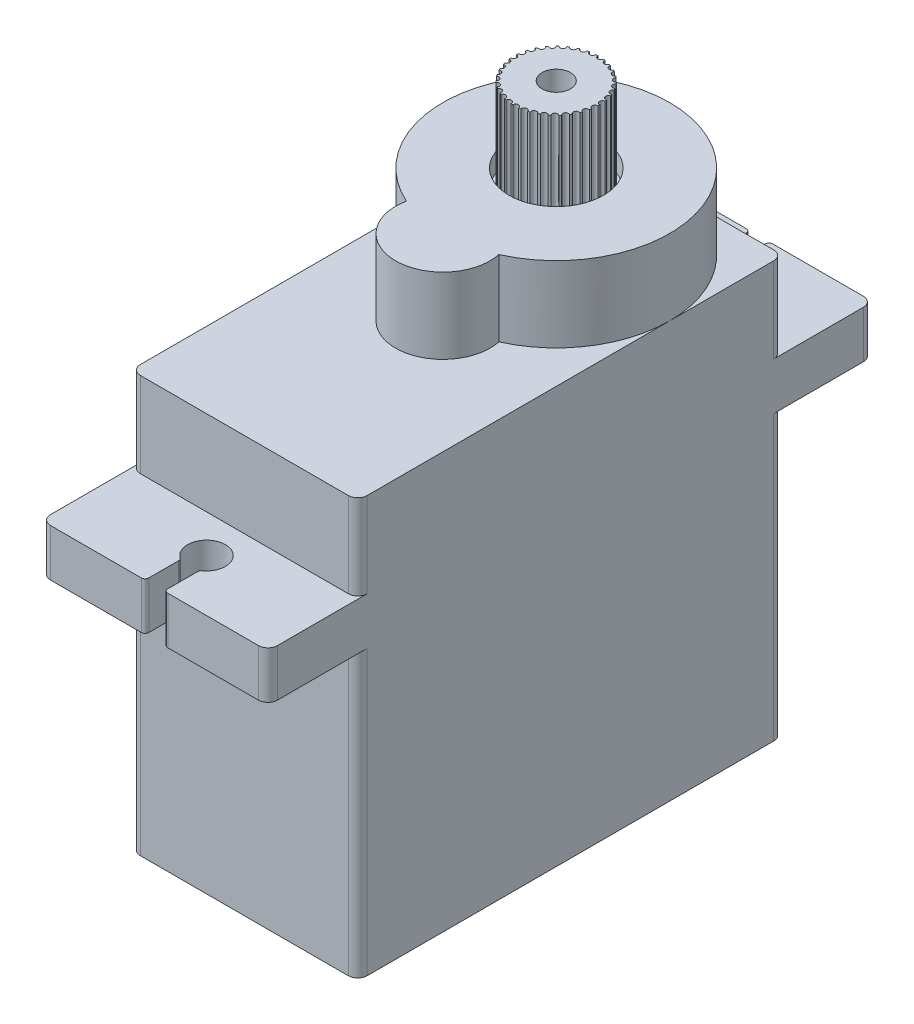
SolidWorks part; units mm, degrees
ref_plane "Ön Düzlem" through (0, 0, 0) normal (0, 0, 1) x (1, 0, 0)
ref_plane "Üst Düzlem" through (0, 0, 0) normal (0, 1, 0) x (1, 0, 0)
ref_plane "Sağ Düzlem" through (0, 0, 0) normal (1, 0, 0) x (0, 0, -1)
sketch "Çizim1" plane through (0, 0, 0) normal (0, 1, 0) x (1, 0, 0)
  line L1 (-5.5, 11.25) -> (5.5, 11.25)
  line L2 (-6, 10.75) -> (-6, -10.75)
  line L3 (-5.5, -11.25) -> (5.5, -11.25)
  line L4 (6, 10.75) -> (6, -10.75)
  line L5 (-6, 11.25) -> (6, -11.25) construction
  line L6 (-6, -11.25) -> (6, 11.25) construction
  arc A0 (5.5, -11.25) -> (6, -10.75) centre (5.5, -10.75) ccw
  arc A1 (-6, -10.75) -> (-5.5, -11.25) centre (-5.5, -10.75) ccw
  arc A2 (5.5, 11.25) -> (6, 10.75) centre (5.5, 10.75) cw
  arc A3 (-5.5, 11.25) -> (-6, 10.75) centre (-5.5, 10.75) ccw
  point P0 (0, 0)
  dimension "D3" = 0.5
  dimension "D1" = 12
  dimension "D2" = 22.5
extrude "Yükseklik-Ekstrüzyon1" add sketch "Çizim1" along normal blind 1
sketch "Çizim2" plane through (0, 1, 0) normal (0, 1, 0) x (1, 0, 0)
  line L0 (-5, 9.25) -> (-5, -9.25)
  line L1 (-5.5, 11.25) -> (5.5, 11.25)
  line L2 (-6, 10.75) -> (-6, -10.75)
  line L3 (-5.5, -11.25) -> (5.5, -11.25)
  line L4 (6, 10.75) -> (6, -10.75)
  line L5 (-6, 11.25) -> (-5.8961, 11.0552) construction
  line L6 (-6, -11.25) -> (-5.8961, -11.0552) construction
  line L7 (-4, -10.25) -> (4, -10.25)
  line L8 (5, 9.25) -> (5, -9.25)
  line L9 (-4, 10.25) -> (4, 10.25)
  line L10 (-6, -11.25) -> (6, -11.25) construction
  line L11 (6, 11.25) -> (6, -11.25) construction
  line L12 (-6, 11.25) -> (-6, -11.25) construction
  line L13 (-6, 11.25) -> (6, 11.25) construction
  line L14 (-5, 10.25) -> (5, 10.25) construction
  line L15 (-5, 10.25) -> (-5, -10.25) construction
  line L16 (-4.9345, 9.2521) -> (4.9345, -9.2521) construction
  line L17 (5, 10.25) -> (5, -10.25) construction
  line L18 (5.8961, 11.0552) -> (6, 11.25) construction
  line L19 (-5, -10.25) -> (5, -10.25) construction
  line L20 (5.8961, -11.0552) -> (6, -11.25) construction
  line L21 (-4.9345, -9.2521) -> (4.9345, 9.2521) construction
  arc A0 (5.5, -11.25) -> (6, -10.75) centre (5.5, -10.75) ccw
  arc A1 (-6, -10.75) -> (-5.5, -11.25) centre (-5.5, -10.75) ccw
  arc A2 (5.5, 11.25) -> (6, 10.75) centre (5.5, 10.75) cw
  arc A3 (-5.5, 11.25) -> (-6, 10.75) centre (-5.5, 10.75) ccw
  arc A5 (4, 10.25) -> (5, 9.25) centre (5, 10.25) ccw
  arc A7 (-4, -10.25) -> (-5, -9.25) centre (-5, -10.25) ccw
  arc A8 (-5, 9.25) -> (-4, 10.25) centre (-5, 10.25) ccw
  arc A9 (5, -9.25) -> (4, -10.25) centre (5, -10.25) ccw
  point P0 (0, 0)
  dimension "D2" = 0.5
  dimension "D1" = 1
extrude "Yükseklik-Ekstrüzyon2" add sketch "Çizim2" along normal blind 5
sketch "Çizim3" plane through (0, 6, 0) normal (0, 1, 0) x (1, 0, 0)
  line L0 (0, -10.25) -> (0, -11.25) construction
  line L1 (-4, -10.25) -> (4, -10.25) construction
  line L2 (-5.5, -11.25) -> (5.5, -11.25) construction
  line L3 (0, -11.25) -> (0, -10.75) construction
  line L4 (0, -10.75) -> (2.4368, -10.75) construction
  line L6 (-2, -10.25) -> (2, -10.25)
  line L7 (-2, -10.25) -> (-2, -11.25)
  line L8 (-2, -11.25) -> (2, -11.25)
  line L9 (2, -10.25) -> (2, -11.25)
  line L10 (-2, -10.25) -> (2, -11.25) construction
  line L11 (-2, -11.25) -> (2, -10.25) construction
  dimension "D1" = 4
extrude "Kes-Ekstrüzyon1" cut sketch "Çizim3" against normal blind 1
fillet "Radyus1" radius 0.1 2 edges at (2, 5, 10.75) (-2, 5, 10.75)
sketch "Çizim4" plane through (0, 6, 0) normal (0, 1, 0) x (1, 0, 0)
  line L0 (-4, 10.25) -> (4, 10.25)
  line L1 (-5.5, 11.25) -> (5.5, 11.25)
  line L2 (-6, 10.75) -> (-6, -10.75)
  line L3 (-5.5, -11.25) -> (5.5, -11.25)
  line L4 (6, 10.75) -> (6, -10.75)
  line L5 (-6, 11.25) -> (-5.8961, 11.0552) construction
  line L6 (-6, -11.25) -> (-5.8961, -11.0552) construction
  line L7 (-4, 10.25) -> (4, 10.25)
  line L8 (5, 9.25) -> (5, -9.25)
  line L9 (5, -9.25) -> (5, 9.25)
  line L10 (-4, 10.25) -> (4, 10.25)
  line L11 (5, 9.25) -> (5, -9.25)
  line L12 (-4, -10.25) -> (4, -10.25)
  line L13 (-5, 9.25) -> (-5, -9.25)
  line L14 (-4.9345, 9.2521) -> (4.9345, -9.2521) construction
  line L15 (-5, 10.25) -> (-5, -10.25) construction
  line L16 (-5, 10.25) -> (5, 10.25) construction
  line L17 (5, 10.25) -> (5, -10.25) construction
  line L18 (5.8961, 11.0552) -> (6, 11.25) construction
  line L19 (5.8961, -11.0552) -> (6, -11.25) construction
  line L20 (-5, -10.25) -> (5, -10.25) construction
  line L21 (-4.9345, -9.2521) -> (4.9345, 9.2521) construction
  arc A0 (5.5, -11.25) -> (6, -10.75) centre (5.5, -10.75) ccw
  arc A1 (-6, -10.75) -> (-5.5, -11.25) centre (-5.5, -10.75) ccw
  arc A2 (5.5, 11.25) -> (6, 10.75) centre (5.5, 10.75) cw
  arc A3 (-5.5, 11.25) -> (-6, 10.75) centre (-5.5, 10.75) ccw
  arc A4 (-5, 9.25) -> (-4, 10.25) centre (-5, 10.25) ccw
  arc A5 (4, 10.25) -> (5, 9.25) centre (5, 10.25) ccw
  arc A6 (-4, -10.25) -> (-5, -9.25) centre (-5, -10.25) ccw
  arc A7 (5, -9.25) -> (4, -10.25) centre (5, -10.25) ccw
  arc A8 (5, 10.25) -> (5, 10.25) centre (5, 10.25) cw
  arc A9 (5, -10.25) -> (5, -10.25) centre (5, -10.25) ccw
  arc A10 (-5, -10.25) -> (-5, -10.25) centre (-5, -10.25) ccw
  arc A11 (-5, 10.25) -> (-5, 10.25) centre (-5, 10.25) ccw
  point P0 (0, 0)
  line M12 (4, -10.25) -> (2, -10.25)
  line M14 (2, -11.25) -> (5.5, -11.25)
  arc M15 (5.5, -11.25) -> (6, -10.75) centre (5.5, -10.75) ccw
  line M16 (6, -10.75) -> (6, 10.75)
  arc M17 (6, 10.75) -> (5.5, 11.25) centre (5.5, 10.75) ccw
  line M18 (5.5, 11.25) -> (-5.5, 11.25)
  arc M19 (-5.5, 11.25) -> (-6, 10.75) centre (-5.5, 10.75) ccw
  line M20 (-6, 10.75) -> (-6, -10.75)
  arc M21 (-6, -10.75) -> (-5.5, -11.25) centre (-5.5, -10.75) ccw
  line M22 (-5.5, -11.25) -> (-2, -11.25)
  line M24 (-2, -10.25) -> (-4, -10.25)
  arc M25 (-4, -10.25) -> (-5, -9.25) centre (-5, -10.25) ccw
  line M26 (-5, -9.25) -> (-5, 9.25)
  arc M27 (-5, 9.25) -> (-4, 10.25) centre (-5, 10.25) ccw
  line M28 (-4, 10.25) -> (4, 10.25)
  arc M29 (4, 10.25) -> (5, 9.25) centre (5, 10.25) ccw
  line M30 (5, 9.25) -> (5, -9.25)
  arc M31 (5, -9.25) -> (4, -10.25) centre (5, -10.25) ccw
  dimension "D1" = 0.5
  dimension "D2" = 1
extrude "Yükseklik-Ekstrüzyon4" add sketch "Çizim4" along normal blind 9 contours M31 M12 M14 M15 M16 M17 M18 M19 M20 M21 M22 M24 M25 M26 M27 M28 M29 M30 | L12 L3 region at (0, 6, -10.995)
sketch "Çizim6" plane through (0, 15, 0) normal (0, 1, 0) x (1, 0, 0)
  line L0 (0, -10.25) -> (0, -12.25) construction
  line L1 (-5.5, 16) -> (-0.7, 16)
  line L2 (-6, 15.5) -> (-6, -15.5)
  line L3 (-5.5, -16) -> (-0.7, -16)
  line L4 (6, 15.5) -> (6, -15.5)
  line L5 (-6, 16) -> (6, -16) construction
  line L6 (-3.8437, -10.25) -> (6, 16) construction
  line L7 (-4, 10.25) -> (4, 10.25)
  line L8 (-5, 9.25) -> (-5, -9.25)
  line L9 (-4, -10.25) -> (4, -10.25)
  line L10 (5, 9.25) -> (5, -9.25)
  line L11 (-4.5616, 9.3512) -> (4.5616, -9.3512) construction
  line L12 (-4.5616, -9.3512) -> (4.5616, 9.3512) construction
  line L13 (0, -12.25) -> (0, -11.25) construction
  line L14 (-5.5, -11.25) -> (5.5, -11.25) construction
  line L15 (0, -11.25) -> (8.7476, -11.25) construction
  line L16 (0, -12.25) -> (8.7476, -12.25) construction
  line L17 (0.7, -16) -> (5.5, -16)
  line L18 (-0.5, -14.2247) -> (-0.5, -15.8)
  line L19 (0.5, -14.2247) -> (0.5, -15.8)
  line L20 (0, 0) -> (5, 0) construction
  line L21 (0.5, 14.2247) -> (0.5, 15.8)
  line L22 (-0.5, 14.2247) -> (-0.5, 15.8)
  line L23 (0.7, 16) -> (5.5, 16)
  arc A0 (-5, 9.25) -> (-4, 10.25) centre (-5, 10.25) ccw
  arc A1 (4, 10.25) -> (5, 9.25) centre (5, 10.25) ccw
  arc A2 (5, -9.25) -> (4, -10.25) centre (5, -10.25) ccw
  arc A3 (-4, -10.25) -> (-5, -9.25) centre (-5, -10.25) ccw
  arc A4 (5.5, -16) -> (6, -15.5) centre (5.5, -15.5) ccw
  arc A5 (-6, -15.5) -> (-5.5, -16) centre (-5.5, -15.5) ccw
  arc A6 (5.5, 16) -> (6, 15.5) centre (5.5, 15.5) cw
  arc A7 (-5.5, 16) -> (-6, 15.5) centre (-5.5, 15.5) ccw
  arc A9 (0.5833, -14.0622) -> (-0.5833, -14.0622) centre (0, -13.25) ccw
  arc A10 (0.5, -14.2247) -> (0.5833, -14.0622) centre (0.7, -14.2247) cw
  arc A11 (-0.5, -14.2247) -> (-0.5833, -14.0622) centre (-0.7, -14.2247) ccw
  arc A12 (0.5, -15.8) -> (0.7, -16) centre (0.7, -15.8) ccw
  arc A13 (-0.5, -15.8) -> (-0.7, -16) centre (-0.7, -15.8) cw
  arc A14 (0.5, 15.8) -> (0.7, 16) centre (0.7, 15.8) cw
  arc A15 (-0.5, 15.8) -> (-0.7, 16) centre (-0.7, 15.8) ccw
  arc A16 (0.5, 14.2247) -> (0.5833, 14.0622) centre (0.7, 14.2247) ccw
  arc A17 (-0.5, 14.2247) -> (-0.5833, 14.0622) centre (-0.7, 14.2247) cw
  arc A18 (0.5833, 14.0622) -> (-0.5833, 14.0622) centre (0, 13.25) cw
  point P0 (0, 0)
  point P6 (0, 0)
  point P54 (0.5, -16)
  dimension "D2" = 0.5
  dimension "D4" = 2
  dimension "D5" = 0.2
  dimension "D1" = 32
  dimension "D3" = 1
extrude "Yükseklik-Ekstrüzyon5" add sketch "Çizim6" along normal blind 2.5
sketch "Çizim7" plane through (0, 17.5, 0) normal (0, 1, 0) x (1, 0, 0)
  line L0 (6, -15.5) -> (6, 15.5) construction
  line L1 (-5.5, 11.25) -> (5.5, 11.25)
  line L2 (-6, 10.75) -> (-6, -10.75)
  line L3 (-5.5, -11.25) -> (5.5, -11.25)
  line L4 (6, 10.75) -> (6, -10.75)
  line L5 (-6, 11.25) -> (-5.8961, 11.0552) construction
  line L6 (-6, -11.25) -> (-5.8961, -11.0552) construction
  line L7 (-5, 9.25) -> (-5, -9.25)
  line L8 (-4, 10.25) -> (4, 10.25)
  line L9 (5, 9.25) -> (5, -9.25)
  line L10 (4, -10.25) -> (-4, -10.25)
  line L12 (-4.9345, 9.2521) -> (4.9345, -9.2521) construction
  line L13 (5.8961, 11.0552) -> (6, 11.25) construction
  line L14 (5.8961, -11.0552) -> (6, -11.25) construction
  line L15 (-5, -9.25) -> (-5, 9.25)
  line L16 (-4.9345, -9.2521) -> (4.9345, 9.2521) construction
  line L17 (-5, 9.25) -> (-5, -9.25)
  arc A0 (-6, -10.75) -> (-5.5, -11.25) centre (-5.5, -10.75) ccw
  arc A1 (5.5, -11.25) -> (6, -10.75) centre (5.5, -10.75) ccw
  arc A2 (5.5, 11.25) -> (6, 10.75) centre (5.5, 10.75) cw
  arc A3 (-5.5, 11.25) -> (-6, 10.75) centre (-5.5, 10.75) ccw
  arc A4 (-5, 9.25) -> (-4, 10.25) centre (-5, 10.25) ccw
  arc A5 (4, 10.25) -> (5, 9.25) centre (5, 10.25) ccw
  arc A6 (5, -9.25) -> (4, -10.25) centre (5, -10.25) ccw
  arc A8 (-4, -10.25) -> (-5, -9.25) centre (-5, -10.25) ccw
  point P0 (0, 0)
  line M16 (6, -15.5) -> (6, 15.5)
  line M28 (-6, 15.5) -> (-6, -15.5)
  line M39 (-5, -9.25) -> (-5, 9.25)
  arc M40 (-5, 9.25) -> (-4, 10.25) centre (-5, 10.25) ccw
  line M41 (-4, 10.25) -> (4, 10.25)
  arc M42 (4, 10.25) -> (5, 9.25) centre (5, 10.25) ccw
  line M43 (5, 9.25) -> (5, -9.25)
  arc M44 (5, -9.25) -> (4, -10.25) centre (5, -10.25) ccw
  line M45 (4, -10.25) -> (-4, -10.25)
  arc M46 (-4, -10.25) -> (-5, -9.25) centre (-5, -10.25) ccw
  dimension "D2" = 0.5
  dimension "D1" = 22.5
extrude "Yükseklik-Ekstrüzyon6" add sketch "Çizim7" along normal blind 3.5 contours L1 A3 A0 L3 A1 A2 M28 M16 M46 M39 M40 M41 M42 M43 M44 M45 region at (0, 17.5, -10.995)
sketch "Çizim8" plane through (0, 21, 0) normal (0, 1, 0) x (1, 0, 0)
  line L0 (6, -15.5) -> (6, -10.75) construction
  line L1 (-5.5, 11.25) -> (5.5, 11.25)
  line L2 (-6, 10.75) -> (-6, -10.75)
  line L3 (-5.5, -11.25) -> (5.5, -11.25)
  line L4 (6, 10.75) -> (6, -10.75)
  line L5 (-6, 11.25) -> (6, -11.25) construction
  line L6 (-6, -11.25) -> (6, 11.25) construction
  arc A0 (-6, -10.75) -> (-5.5, -11.25) centre (-5.5, -10.75) ccw
  arc A1 (5.5, -11.25) -> (6, -10.75) centre (5.5, -10.75) ccw
  arc A2 (5.5, 11.25) -> (6, 10.75) centre (5.5, 10.75) cw
  arc A3 (-5.5, 11.25) -> (-6, 10.75) centre (-5.5, 10.75) ccw
  point P0 (0, 0)
  dimension "D1" = 0.5
extrude "Yükseklik-Ekstrüzyon7" add sketch "Çizim8" along normal blind 1
sketch "Çizim9" plane through (0, 22, 0) normal (0, 1, 0) x (1, 0, 0)
  line L0 (-6, 5.25) -> (6, 5.25) construction
  line L1 (-6, 10.75) -> (-6, -10.75) construction
  line L2 (6, -10.75) -> (6, 10.75) construction
  line L3 (5.5, 11.25) -> (-5.5, 11.25) construction
  line L4 (0, 5.25) -> (0, -0.75) construction
  arc A0 (2.4451, -0.2292) -> (-2.4451, -0.2292) centre (0, 5.25) ccw
  arc A1 (-2.4451, -0.2292) -> (2.4451, -0.2292) centre (0, -0.75) ccw
  arc A2 (1.0153, 0.3542) -> (-1.0153, 0.3542) centre (0, 5.25) ccw
  arc A3 (-1.0153, 0.3542) -> (1.0153, 0.3542) centre (0, -0.75) ccw
  dimension "D2" = 5
  dimension "D1" = 6
  dimension "D3" = 1
extrude "Kes-Ekstrüzyon2" cut sketch "Çizim9" against normal blind 1 contours A2 A3
extrude "Yükseklik-Ekstrüzyon8" add sketch "Çizim9<3>" along normal blind 3
sketch "Çizim9<3>" plane through (0, 22, 0) normal (0, 1, 0) x (1, 0, 0) same geometry as "Çizim9"
fillet "Radyus2" radius 0.5 2 edges at (1.0153, 23, -0.3542) (-1.0153, 23, -0.3542)
sketch "Çizim10" plane through (0, 25, 0) normal (0, 1, 0) x (1, 0, 0)
  arc A0 (2.4451, -0.2292) -> (-2.4451, -0.2292) centre (0, 5.25) ccw
  arc A1 (-2.4451, -0.2292) -> (2.4451, -0.2292) centre (0, -0.75) ccw
extrude "Yükseklik-Ekstrüzyon9" add sketch "Çizim10" along normal blind 1
sketch "Çizim11" plane through (0, 26, 0) normal (0, 1, 0) x (1, 0, 0)
  circle A0 centre (0, 5.25) radius 2.5
  dimension "D1" = 5
extrude "Kes-Ekstrüzyon3" cut sketch "Çizim11" against normal blind 10
sketch "Çizim15" plane through (0, 26, 0) normal (0, 1, 0) x (1, 0, 0)
  circle A0 centre (0, -0.75) radius 0.25
  dimension "D1" = 0.5
extrude "Yükseklik-Ekstrüzyon12" add sketch "Çizim15" against normal blind 11
ref_plane "Düzlem3" through (0, 30, 0) normal (0, 1, 0) x (1, 0, 0)
sketch "Çizim19" plane through (0, 30, 0) normal (0, 1, 0) x (1, 0, 0)
  circle A0 centre (0, 5.25) radius 2.25
  dimension "D1" = 4.5
extrude "Yükseklik-Ekstrüzyon17" add sketch "Çizim19" against normal blind 5 separate body
sketch "Çizim20" plane through (0, 25, 0) normal (0, -1, 0) x (1, 0, 0)
  circle A0 centre (0, -5.25) radius 4.75
  dimension "D1" = 9.5
extrude "Yükseklik-Ekstrüzyon18" add sketch "Çizim20" along normal blind 3
sketch "Çizim21" plane through (0, 30, 0) normal (0, 1, 0) x (1, 0, 0)
  circle A0 centre (0, 5.25) radius 0.75
  dimension "D1" = 1.5
extrude "Kes-Ekstrüzyon5" cut sketch "Çizim21" against normal blind 10
ref_plane "Düzlem4" through (0, 25.5, 0) normal (0, 1, 0) x (1, 0, 0)
sketch "Çizim22" plane through (0, 25.5, 0) normal (0, 1, 0) x (1, 0, 0)
  line L0 (0, 11.25) -> (0, -3.25) construction
  arc A0 (2.4451, -0.2292) -> (-2.4451, -0.2292) centre (0, 5.25) ccw construction
  arc A1 (-2.4451, -0.2292) -> (2.4451, -0.2292) centre (0, -0.75) ccw construction
  circle A2 centre (0, -0.75) radius 0.5
  dimension "D1" = 1
extrude "Yükseklik-Ekstrüzyon19" add sketch "Çizim22" against normal blind 5
sketch "Çizim23" plane through (0, 20.5, 0) normal (0, -1, 0) x (1, 0, 0)
  circle A0 centre (0, 0.75) radius 4
  dimension "D1" = 8
extrude "Yükseklik-Ekstrüzyon20" add sketch "Çizim23" along normal blind 2
sketch "Çizim24" plane through (0, 22, 0) normal (0, -1, 0) x (1, 0, 0)
  circle A0 centre (0, -5.25) radius 0.75
extrude "Yükseklik-Ekstrüzyon21" add sketch "Çizim24" along normal blind 7 separate body
ref_plane "Düzlem5" through (0, 19, 0) normal (0, -1, 0) x (-1, 0, 0)
sketch "Çizim25" plane through (0, 19, 0) normal (0, -1, 0) x (-1, 0, 0)
  circle A0 centre (0, 5.25) radius 3.5
  dimension "D1" = 7
extrude "Yükseklik-Ekstrüzyon22" add sketch "Çizim25" along normal blind 1
ref_plane "Düzlem6" through (0, 17.5, 0) normal (0, -1, 0) x (-1, 0, 0)
sketch "Çizim26" plane through (0, 17.5, 0) normal (0, -1, 0) x (-1, 0, 0)
  circle A0 centre (0, -0.75) radius 4.5
  dimension "D1" = 9
extrude "Yükseklik-Ekstrüzyon23" add sketch "Çizim26" along normal blind 1
sketch "Çizim32" plane through (0, 0, 10.25) normal (0, 0, -1) x (-1, 0, 0)
  line L1 (2, 6) -> (-2, 6)
  line L2 (2, 6) -> (2, 5.1)
  line L3 (1.9, 5) -> (-1.9, 5)
  line L4 (-2, 6) -> (-2, 5.1)
  arc A0 (-1.9, 5) -> (-2, 5.1) centre (-1.9, 5.1) cw
  arc A1 (2, 5.1) -> (1.9, 5) centre (1.9, 5.1) cw
  point P7 (-2, 5)
  dimension "D3" = 0.1
  dimension "D1" = 1
  dimension "D2" = 4
extrude "Kes-Ekstrüzyon7" cut sketch "Çizim32" along normal blind 30
sketch "Çizim33" plane through (0, 0, 11.25) normal (0, 0, 1) x (1, 0, 0)
  line L1 (-2, 6) -> (2, 6)
  line L2 (-2, 6) -> (-2, 5.1)
  line L3 (-1.9, 5) -> (1.9, 5)
  line L4 (2, 6) -> (2, 5.1)
  arc A0 (1.9, 5) -> (2, 5.1) centre (1.9, 5.1) ccw
  arc A1 (-2, 5.1) -> (-1.9, 5) centre (-1.9, 5.1) ccw
  point P7 (2, 5)
  point P10 (-2, 5)
  dimension "D3" = 0.1
  dimension "D1" = 1
  dimension "D2" = 4
extrude "Yükseklik-Ekstrüzyon33" add sketch "Çizim33" against normal blind 1
sketch "Çizim34" plane through (0, 1, 0) normal (0, 1, 0) x (1, 0, 0)
  line L0 (-5, -6.25) -> (5, -6.25) construction
  line L1 (-5, 9.25) -> (-5, -9.25) construction
  line L2 (5, -9.25) -> (5, 9.25) construction
  line L3 (-4, -10.25) -> (4, -10.25) construction
  line L5 (-3, -3.25) -> (3, -3.25)
  line L6 (-4, -4.25) -> (-4, -8.25)
  line L7 (-3, -9.25) -> (3, -9.25)
  line L8 (4, -4.25) -> (4, -8.25)
  line L9 (-4, -3.25) -> (4, -9.25) construction
  line L10 (-4, -9.25) -> (4, -3.25) construction
  arc A0 (3, -9.25) -> (4, -8.25) centre (3, -8.25) ccw
  arc A1 (-4, -8.25) -> (-3, -9.25) centre (-3, -8.25) ccw
  arc A2 (3, -3.25) -> (4, -4.25) centre (3, -4.25) cw
  arc A3 (-3, -3.25) -> (-4, -4.25) centre (-3, -4.25) ccw
  point P8 (0, -6.25)
  dimension "D4" = 1
  dimension "D1" = 4
  dimension "D2" = 6
  dimension "D3" = 8
extrude "Yükseklik-Ekstrüzyon34" add sketch "Çizim34" along normal blind 14
ref_plane "Düzlem8" through (0, 1, 0) normal (0, -1, 0) x (-1, 0, 0)
sketch "Çizim37" plane through (0, 1, 0) normal (0, -1, 0) x (-1, 0, 0)
  line L0 (4, -6.25) -> (-4, -6.25) construction
  line L1 (4, -4.25) -> (4, -8.25) construction
  line L2 (-4, -8.25) -> (-4, -4.25) construction
  line L4 (4, -9.25) -> (-4, -9.25)
  line L5 (4, -9.25) -> (4, -3.25)
  line L6 (4, -3.25) -> (-4, -3.25)
  line L7 (-4, -9.25) -> (-4, -3.25)
  line L8 (4, -9.25) -> (-4, -3.25) construction
  line L9 (4, -3.25) -> (-4, -9.25) construction
  point P6 (0, -6.25)
  dimension "D1" = 6
  dimension "D2" = 8
extrude "Yükseklik-Ekstrüzyon36" add sketch "Çizim37" against normal blind 1
ref_plane "Düzlem9" through (0, 0, -10.75) normal (0, 0, -1) x (-1, 0, 0)
sketch "Çizim39" plane through (0, 0, -10.75) normal (0, 0, -1) x (-1, 0, 0)
  line L0 (0, 0) -> (0, 6.0146) construction
  line L1 (-5.5, 0) -> (5.5, 0) construction
  line L2 (-2, 6.0146) -> (2, 6.0146)
  line L4 (-2, 6.0146) -> (-2, 5.0146)
  line L5 (-2, 5.0146) -> (2, 5.0146)
  line L6 (2, 6.0146) -> (2, 5.0146)
  line L7 (0, 6.0146) -> (2, 5.0146) construction
  line L8 (-2, 5.0146) -> (0, 6.0146) construction
extrude "Yükseklik-Ekstrüzyon37" add sketch "Çizim39" along normal blind 0.1
sketch "Çizim40" plane through (0, 0, -10.85) normal (0, 0, -1) x (-1, 0, 0)
  line L0 (-2, 5.55) -> (2, 5.55) construction
  line L1 (-2, 6) -> (-2, 5.1) construction
  line L2 (2, 5.1) -> (2, 6) construction
  circle A0 centre (0, 5.55) radius 0.4
  circle A1 centre (1, 5.55) radius 0.4
  circle A2 centre (-1, 5.55) radius 0.4
  dimension "D1" = 0.8
  dimension "D2" = 1
  dimension "D3" = 1
extrude "Yükseklik-Ekstrüzyon38" add sketch "Çizim40" along normal blind 2
sketch "Çizim41" plane through (0, 30, 0) normal (0, 1, 0) x (1, 0, 0)
  line L0 (0, 5.25) -> (-2.25, 5.25) construction
  circle A0 centre (0, 5.25) radius 2.25
  circle A1 centre (-2.25, 5.25) radius 0.15
  circle A2 centre (-2.2138, 5.6518) radius 0.15
  circle A3 centre (-2.1065, 6.0406) radius 0.15
  circle A4 centre (-1.9315, 6.404) radius 0.15
  circle A5 centre (-1.6944, 6.7304) radius 0.15
  circle A6 centre (-1.4029, 7.0091) radius 0.15
  circle A7 centre (-1.0662, 7.2313) radius 0.15
  circle A8 centre (-0.6953, 7.3899) radius 0.15
  circle A9 centre (-0.302, 7.4796) radius 0.15
  circle A10 centre (0.1009, 7.4977) radius 0.15
  circle A11 centre (0.5007, 7.4436) radius 0.15
  circle A12 centre (0.8843, 7.3189) radius 0.15
  circle A13 centre (1.2395, 7.1278) radius 0.15
  circle A14 centre (1.5549, 6.8763) radius 0.15
  circle A15 centre (1.8203, 6.5725) radius 0.15
  circle A16 centre (2.0272, 6.2262) radius 0.15
  circle A17 centre (2.1689, 5.8486) radius 0.15
  circle A18 centre (2.2409, 5.4517) radius 0.15
  circle A19 centre (2.2409, 5.0483) radius 0.15
  circle A20 centre (2.1689, 4.6514) radius 0.15
  circle A21 centre (2.0272, 4.2738) radius 0.15
  circle A22 centre (1.8203, 3.9275) radius 0.15
  circle A23 centre (1.5549, 3.6237) radius 0.15
  circle A24 centre (1.2395, 3.3722) radius 0.15
  circle A25 centre (0.8843, 3.1811) radius 0.15
  circle A26 centre (0.5007, 3.0564) radius 0.15
  circle A27 centre (0.1009, 3.0023) radius 0.15
  circle A28 centre (-0.302, 3.0204) radius 0.15
  circle A29 centre (-0.6953, 3.1101) radius 0.15
  circle A30 centre (-1.0662, 3.2687) radius 0.15
  circle A31 centre (-1.4029, 3.4909) radius 0.15
  circle A32 centre (-1.6944, 3.7696) radius 0.15
  circle A33 centre (-1.9315, 4.096) radius 0.15
  circle A34 centre (-2.1065, 4.4594) radius 0.15
  circle A35 centre (-2.2138, 4.8482) radius 0.15
  point P75 (0, 5.25)
  circle M3 centre (0, 5.25) radius 2.25
  dimension "D1" = 0.3
  dimension "D2" = 35
extrude "Kes-Ekstrüzyon8" cut sketch "Çizim41" against normal blind 5 contours A1 A0 M3 | A1 L0 A0 | L0 A1 M3 | A3 | A2 | A35 | A34 | A33 | A32 | A31 | A30 | A29 | A28 | A27 | A26 | A25 | A24 | A23 | A22 | A21 | A20 | A19 | A18 | A17 | A16 | A15 | A14 | A13 | A12 | A11 | A10 | A9 | A8 | A7 | A6 | A5 | A4 region at (-2.1854, 30, -5.187) region at (-2.1854, 30, -5.313) region at (-2.3128, 30, -5.25)
sketch "Sketch1" plane through (0, 30, 0) normal (0, 1, 0) x (1, 0, 0)
  line L0 (-0.1528, 7.4948) -> (-0.049, 7.4995)
